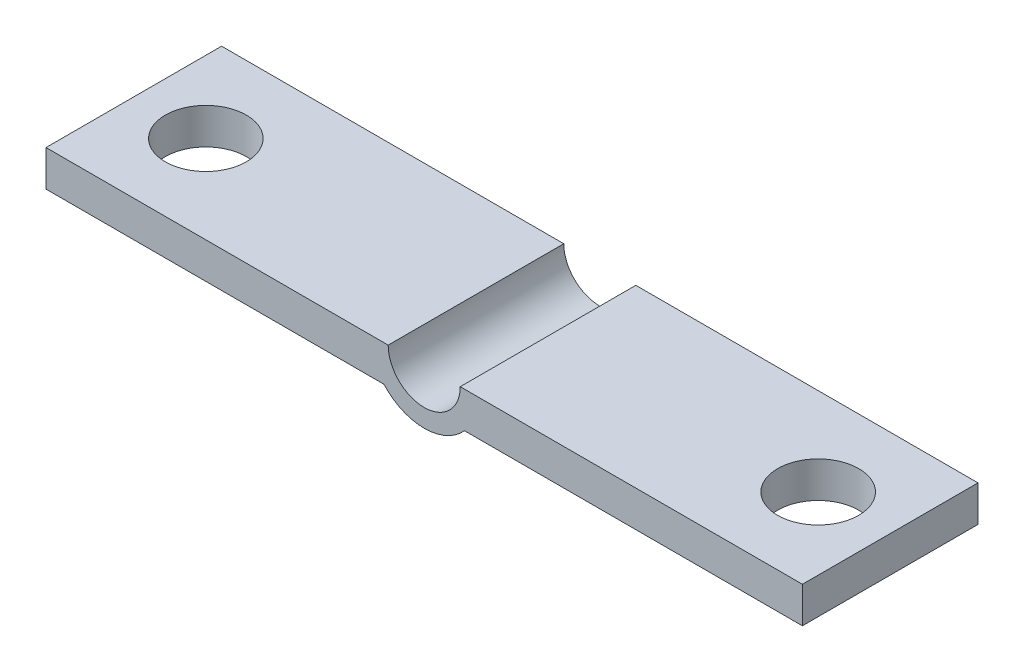
SolidWorks part; units mm, degrees
ref_plane "Front Plane" through (0, 0, 0) normal (0, 0, 1) x (1, 0, 0)
ref_plane "Top Plane" through (0, 0, 0) normal (0, 1, 0) x (1, 0, 0)
ref_plane "Right Plane" through (0, 0, 0) normal (1, 0, 0) x (0, 0, -1)
sketch "Sketch1" plane through (0, 0, 0) normal (0, 0, 1) x (1, 0, 0)
  arc A0 (-2, 0) -> (2, 0) centre (0, 0) ccw
extrude "Extrude-Thin1" add sketch "Sketch1" along normal blind 9.75 thin thin type one direction wall 1
sketch "Sketch3" plane through (0, 0, 0) normal (0, 1, 0) x (1, 0, 0)
  line L1 (-21, 0) -> (-2, 0)
  line L2 (-21, 0) -> (-21, -9.75)
  line L3 (-21, -9.75) -> (-2, -9.75)
  line L4 (21, 0) -> (21, -9.75)
  line L5 (2, -9.75) -> (3, -9.75) construction
  line L6 (2, 0) -> (3, 0) construction
  line L7 (-2, 0) -> (-2, -9.75)
  line L8 (2, 0) -> (2, -9.75)
  line L9 (2, 0) -> (21, 0)
  line L10 (2, -9.75) -> (21, -9.75)
  dimension "D1" = 42
extrude "Boss-Extrude1" add sketch "Sketch3" against normal blind 2
sketch "Sketch4" plane through (0, 0, 0) normal (0, 1, 0) x (1, 0, 0)
  line L0 (-21, 0) -> (-21, -9.75) construction
  line L1 (-21, 0) -> (-2, 0) construction
  line L2 (0, -55) -> (0, 55) construction
  circle A0 centre (-17, -4.875) radius 2.25
  circle A1 centre (17, -4.875) radius 2.25
  point P2 (-14.9153, -4.7519)
  point P5 (0, 0)
  point P6 (0, 0)
  dimension "D2" = 4.875
  dimension "D1" = 4
extrude "Cut-Extrude1" cut sketch "Sketch4" against normal through all
